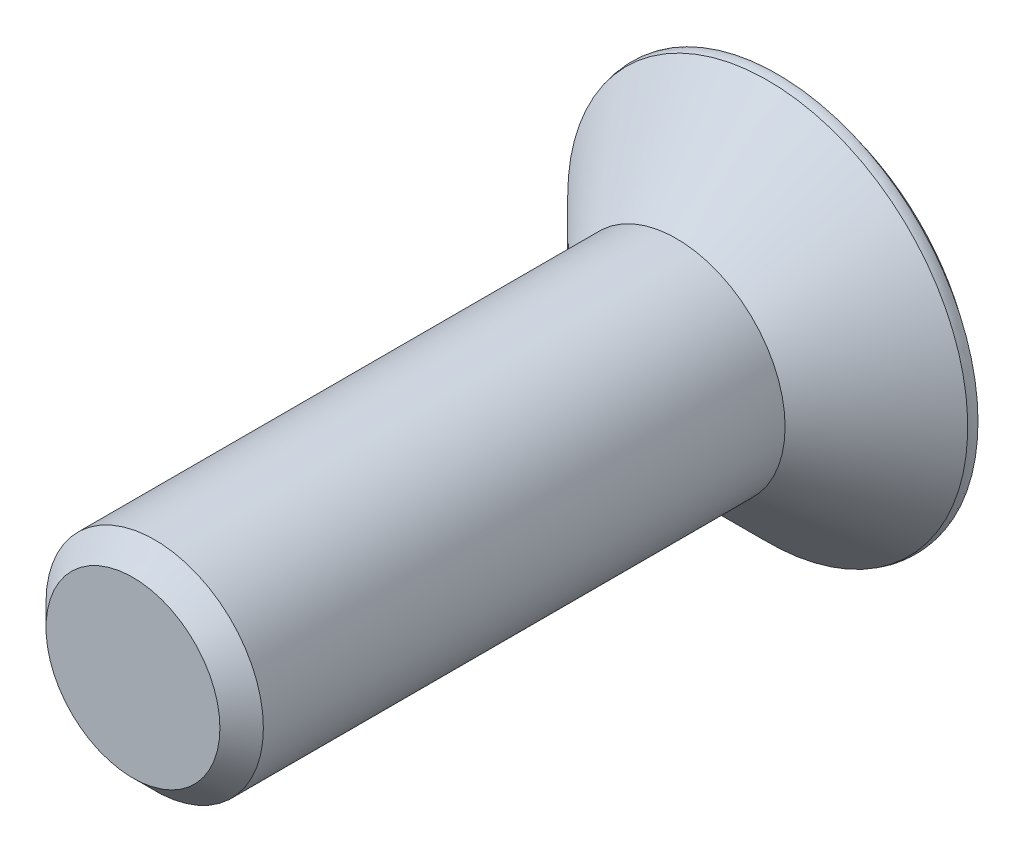
SolidWorks part; units mm, degrees
ref_plane "Plan1" through (0, 0, 0) normal (0, 0, 1) x (1, 0, 0)
ref_plane "Plan2" through (0, 0, 0) normal (0, 1, 0) x (1, 0, 0)
ref_plane "Plan3" through (0, 0, 0) normal (1, 0, 0) x (0, 0, -1)
ref_axis "Z Axis" through (0, 0, -50) along (0, 0, 1)
sketch "Esquisse1" plane through (0, 0, 0) normal (0, 1, 0) x (1, 0, 0)
  line L0 (0, 0) -> (0, 3.1) construction
  line L1 (0, 0) -> (2, 0)
  line L2 (0, 0) -> (0, 3.1696)
  line L3 (0, 0) -> (0, 3.1) construction
  line L5 (3.7, 0) -> (3.7, 3.1) construction
  line L6 (0, 3.1696) -> (0, -3.8625) construction
  line L7 (3.6803, 1.6803) -> (2, 0)
  arc A1 (3.6915, 1.8581) -> (3.6803, 1.6803) centre (3.4, 1.7873) cw
  arc A2 (3.6915, 1.8581) -> (0, 3.1696) centre (0, -2.6816) ccw
  point P9 (3.7, 1.55)
  dimension "D3" = 3.7
  dimension "D1" = 0.3
  dimension "D2" = 3.1
  dimension "D4" = 2
  dimension "D5" = 135
revolve "Base-Révolution" add sketch "Esquisse1" angle 360 about L0 reverse direction yes
ref_plane "Plan4" through (0, 0, -3.1) normal (0, 0, 1) x (1, 0, 0)
sketch "Esquisse2" plane through (0, 0, -3.1) normal (0, 0, 1) x (1, 0, 0)
  line L0 (0.6, -0.6) -> (0.6, -2.35)
  line L1 (-2.35, 0.6) -> (-0.6, 0.6)
  line L2 (-2.35, 0.6) -> (-2.35, -0.6)
  line L3 (-2.35, -0.6) -> (-0.6, -0.6)
  line L4 (2.35, 0.6) -> (2.35, -0.6)
  line L5 (-0.6, 2.35) -> (0.6, 2.35)
  line L6 (-0.6, 2.35) -> (-0.6, 0.6)
  line L7 (-0.6, -2.35) -> (0.6, -2.35)
  line L8 (0.6, 2.35) -> (0.6, 0.6)
  line L9 (0.6, 0.6) -> (2.35, 0.6)
  line L10 (-0.6, -0.6) -> (-0.6, -2.35)
  line L11 (0.6, -0.6) -> (2.35, -0.6)
  dimension "D2" = 4.7
  dimension "D3" = 2.35
  dimension "D4" = 2.35
  dimension "D5" = 4.7
extrude "Enlev. mat.-Extru.1" cut sketch "Esquisse2" along normal blind 1 and the other way blind 10
sketch "Esquisse3" plane through (0, 0, 0) normal (0, 1, 0) x (1, 0, 0)
  line L1 (0, 0) -> (0, -10) construction
  line L2 (0, 0) -> (2, 0)
  line L3 (0, 0) -> (0, -10)
  line L4 (0, -10) -> (2, -10)
  line L6 (2, 0) -> (2, -10)
  dimension "D1" = 10
  dimension "D2" = 2
revolve "Boss.-Révol.1" add sketch "Esquisse3" angle 360 about L1 reverse direction yes
sketch "Esquisse4" plane through (0, 0, 0) normal (0, 1, 0) x (1, 0, 0)
  line L0 (1.3, -10.0488) -> (1.3, -9.9512)
  line L2 (1.3, -9.9512) -> (2.07, -9.5066)
  line L3 (1.3, -10.0488) -> (2.07, -10.4934)
  line L4 (2.07, -9.5066) -> (2.07, -10.4934)
  line L6 (-2, -10) -> (2, -10) construction
  point P4 (2, -10)
  dimension "D2" = 0.0488
  dimension "D3" = 0.0488
  dimension "D4" = 0.77
  dimension "D5" = 60
  dimension "D1" = 0.7
  dimension "D6" = 60
chamfer "Chanfrein1" distance 0.4 angle 45 1 edges at (2, 0, 10)
sketch "Esquisse5" plane through (0, 0, 10) normal (0, 0, 1) x (1, 0, 0)
  circle A0 centre (0, 0) radius 2 construction
  circle A1 centre (0, 0) radius 2
curve "Hélice1" pitch 1 height 10 turns 10
sweep "Enlèvement de matière-Balayage1" [suppressed] cut profiles "Esquisse4" path "Hélice1"
sketch "Esquisse6" plane through (0, 0, -2.1) normal (0, 0, -1) x (-1, 0, 0)
  line L10 (2.35, 0.6) -> (0.6, 0.6)
  line L11 (2.35, 0.6) -> (0.6, 0.6)
  line L14 (0.6, 0.6) -> (0.6, 2.35)
  line L15 (-0.6, 2.35) -> (-0.6, 0.6)
  line L16 (-0.6, 2.35) -> (-0.6, 0.6)
  line L17 (-0.6, 0.6) -> (-2.35, 0.6)
  line L18 (2.35, -0.6) -> (2.35, 0.6)
  line L19 (2.35, -0.6) -> (2.35, 0.6)
  line L20 (-0.6, -0.6) -> (-0.6, -2.35)
  line L21 (0.6, 2.35) -> (-0.6, 2.35)
  line L22 (0.6, 2.35) -> (-0.6, 2.35)
  line L23 (0.6, -0.6) -> (2.35, -0.6)
  line L24 (-2.35, 0.6) -> (-2.35, -0.6)
  line L25 (-2.35, 0.6) -> (-2.35, -0.6)
  line L26 (0.6, 0.6) -> (0.6, 2.35)
  line L27 (-2.35, -0.6) -> (-0.6, -0.6)
  line L28 (-2.35, -0.6) -> (-0.6, -0.6)
  line L29 (-0.6, 0.6) -> (-2.35, 0.6)
  line L30 (-0.6, -2.35) -> (0.6, -2.35)
  line L31 (-0.6, -2.35) -> (0.6, -2.35)
  line L32 (-0.6, -0.6) -> (-0.6, -2.35)
  line L33 (0.6, -2.35) -> (0.6, -0.6)
  line L34 (0.6, -2.35) -> (0.6, -0.6)
  line L35 (0.6, -0.6) -> (2.35, -0.6)
  dimension "D1" = 0
extrude "Enlèv. mat.-Extru.1" cut sketch "Esquisse6" against normal blind 1
equation "\"D1@Chanfrein1\"=\"D2@Esquisse3\"*0.2"
equation "\"D4@Esquisse4\"=1.1*\"D1@Esquisse4\""
equation "\"D1@Plan4\"=\"D2@Esquisse1\""
